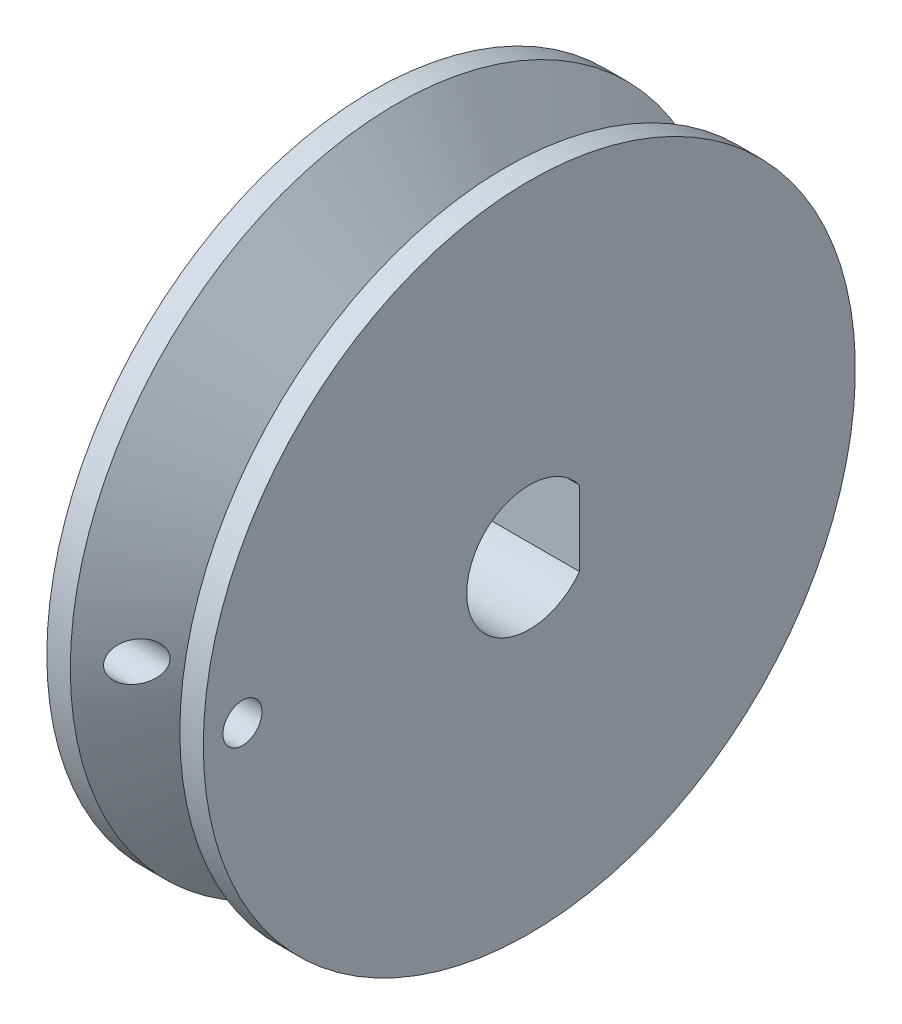
SolidWorks part; units mm, degrees
ref_plane "Front Plane" through (0, 0, 0) normal (0, 0, 1) x (1, 0, 0)
ref_plane "Top Plane" through (0, 0, 0) normal (0, 1, 0) x (1, 0, 0)
ref_plane "Right Plane" through (0, 0, 0) normal (1, 0, 0) x (0, 0, -1)
sketch "Sketch2" plane through (0, 0, 0) normal (0, 0, 1) x (1, 0, 0)
  line L0 (0, 0) -> (28.9983, 0) construction
  line L1 (0, 0) -> (0, 15.875)
  line L2 (0, 15.875) -> (1.143, 15.875)
  line L3 (1.143, 15.875) -> (3.81, 12.065)
  line L4 (3.81, 12.065) -> (6.477, 15.875)
  line L5 (6.477, 15.875) -> (7.62, 15.875)
  line L6 (7.62, 15.875) -> (7.62, 0)
  line L7 (0, 12.065) -> (7.62, 12.065) construction
  line L8 (0, 0) -> (7.62, 0)
  dimension "D1" = 1.143
  dimension "D2" = 15.875
  dimension "D3" = 7.62
  dimension "D4" = 3.81
revolve "Revolve1" add sketch "Sketch2" angle 360 about L0
sketch "Sketch3" plane through (7.62, 0, 0) normal (1, 0, 0) x (0, 0, -1)
  line L0 (2.4409, -1.8254) -> (2.4409, 1.8254)
  line L1 (3.048, 2.5745) -> (3.048, -1.9178) construction
  arc A0 (2.4409, 1.8254) -> (2.4409, -1.8254) centre (0, 0) ccw
  arc A1 (2.4409, 1.8254) -> (2.4409, -1.8254) centre (0, 0) cw construction
  dimension "D2" = 3.048
  dimension "D1" = 0.6071
extrude "Cut-Extrude1" cut sketch "Sketch3" against normal through all both and the other way through all
sketch "Sketch4" plane through (7.62, 0, 0) normal (1, 0, 0) x (0, 0, -1)
  line L0 (-12.065, 0) -> (-15.875, 0) construction
  circle A0 centre (0, 0) radius 12.065 construction
  circle A1 centre (0, 0) radius 12.065 construction
  circle A2 centre (-13.97, 0) radius 0.9525
  circle A3 centre (0, 0) radius 15.875 construction
  dimension "D1" = 1.905
extrude "Cut-Extrude2" cut sketch "Sketch4" against normal through all both and the other way through all
